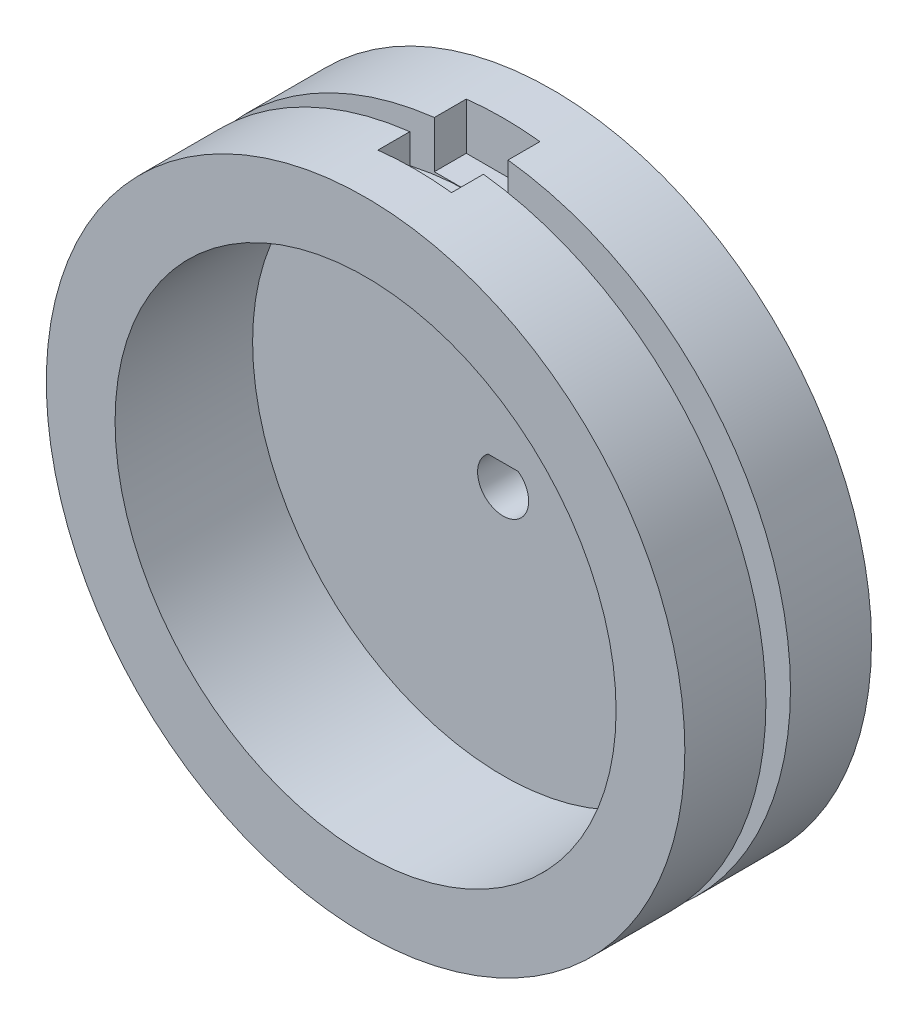
SolidWorks part; units mm, degrees
ref_plane "Front Plane" through (0, 0, 0) normal (0, 0, 1) x (1, 0, 0)
ref_plane "Top Plane" through (0, 0, 0) normal (0, 1, 0) x (1, 0, 0)
ref_plane "Right Plane" through (0, 0, 0) normal (1, 0, 0) x (0, 0, -1)
sketch "Sketch2" plane through (0, 0, 0) normal (1, 0, 0) x (0, 0, -1)
  line L0 (0, 0) -> (0, 32.5)
  line L1 (0, 32.5) -> (-8.25, 32.5)
  line L2 (-19, 32.5) -> (-19, 25.5)
  line L3 (-19, 25.5) -> (-5, 25.5)
  line L4 (-5, 25.5) -> (-5, 0)
  line L5 (-5, 0) -> (0, 0)
  line L6 (-8.25, 32.5) -> (-8.25, 27.5)
  line L7 (-8.25, 27.5) -> (-10.75, 27.5)
  line L8 (-10.75, 27.5) -> (-10.75, 32.5)
  line L9 (-10.75, 32.5) -> (-19, 32.5)
  dimension "D1" = 19
  dimension "D2" = 32.5
  dimension "D3" = 7
  dimension "D4" = 5
  dimension "D5" = 2.5
  dimension "D6" = 8.25
  dimension "D7" = 5
revolve "Revolve1" add sketch "Sketch2" angle 360 about L5
ref_plane "Plane1" through (0, 32.5, 0) normal (0, 1, 0) x (1, 0, 0)
sketch "Sketch7" plane through (0, 32.5, 0) normal (0, 1, 0) x (1, 0, 0)
  line L1 (-3.75, -14) -> (3.75, -14)
  line L2 (-3.75, -14) -> (-3.75, -5)
  line L3 (-3.75, -5) -> (3.75, -5)
  line L4 (3.75, -14) -> (3.75, -5)
  line L5 (-3.75, -9.5) -> (3.75, -9.5) construction
  line L6 (32.5, 0) -> (-32.5, 0) construction
  line L7 (0, -5) -> (0, 0) construction
  dimension "D1" = 9.5
  dimension "D2" = 9
  dimension "D3" = 7.5
extrude "Cut-Extrude1" cut sketch "Sketch7" against normal blind 5
mirror "Mirror1" about plane through (0, 0, 0) normal (0, 1, 0) of "Cut-Extrude1"
sketch "Sketch8" plane through (0, 0, 0) normal (0, 0, -1) x (-1, 0, 0)
  line L0 (-1.533, 2.1) -> (1.533, 2.1)
  arc A0 (-1.533, 2.1) -> (1.533, 2.1) centre (0, 0) ccw
  dimension "D1" = 5.2
  dimension "D2" = 2.1
extrude "Cut-Extrude2" cut sketch "Sketch8" against normal through all
